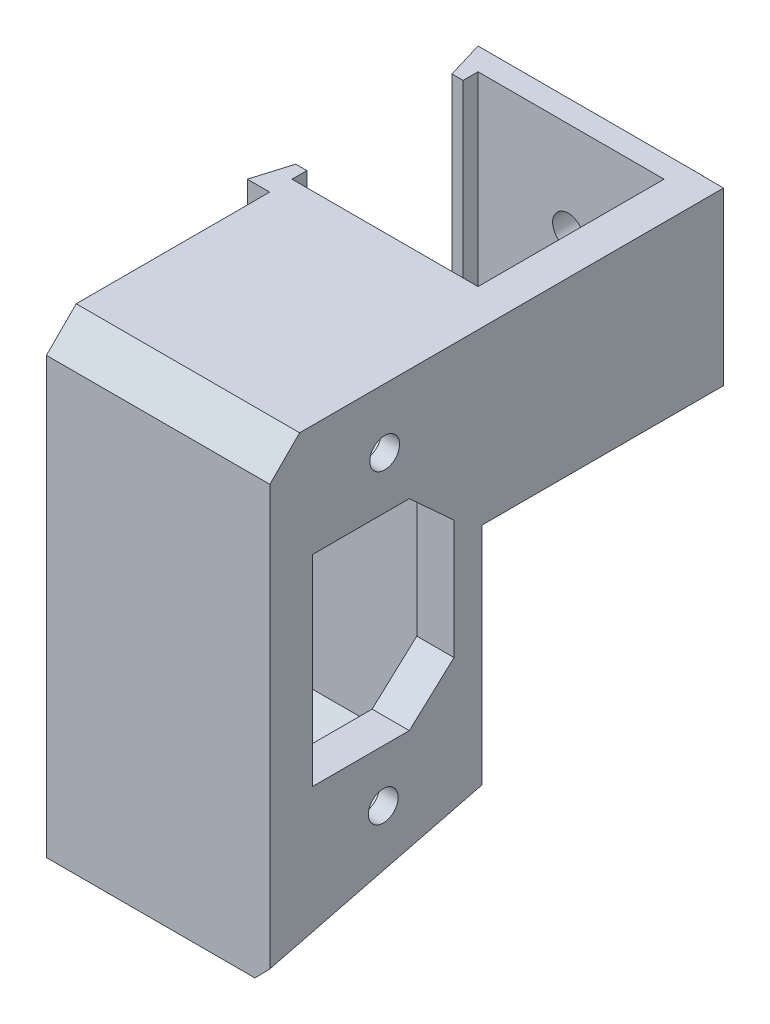
SolidWorks part; units mm, degrees
ref_plane "Спереди" through (0, 0, 0) normal (0, 0, 1) x (1, 0, 0)
ref_plane "Сверху" through (0, 0, 0) normal (0, 1, 0) x (1, 0, 0)
ref_plane "Справа" through (0, 0, 0) normal (1, 0, 0) x (0, 0, -1)
sketch "Эскиз1" plane through (0, 0, 0) normal (0, 1, 0) x (1, 0, 0)
  line L0 (-66.8258, 34.9697) -> (-66.8258, 29.9697)
  line L1 (-63.8258, 29.9697) -> (-63.8258, 31.9697)
  line L2 (-63.8258, 31.9697) -> (-38.8258, 31.9697)
  line L3 (-38.8258, 31.9697) -> (-38.8258, 6.9697)
  line L4 (-38.8258, 6.9697) -> (-63.8258, 6.9697)
  line L5 (-63.8258, 6.9697) -> (-63.8258, 8.9697)
  line L6 (-63.8258, 8.9697) -> (-66.8258, 8.9697)
  line L7 (-66.8258, 8.9697) -> (-66.8258, 3.9697)
  line L8 (-66.8258, 3.9697) -> (-22.1235, 3.9697)
  line L9 (-22.1235, 3.9697) -> (-36.579, 34.9697)
  line L10 (-36.579, 34.9697) -> (-66.8258, 34.9697)
  line L11 (-66.8258, 29.9697) -> (-63.8258, 29.9697)
  point P13 (0, 0)
  point P14 (-63.7308, 29.7758)
  dimension "D1" = 25
  dimension "D2" = 25
  dimension "D3" = 25
  dimension "D4" = 155
  dimension "D5" = 3
  dimension "D6" = 3
  dimension "D7" = 3
  dimension "D8" = 3
  dimension "D9" = 2
  dimension "D10" = 2
extrude "Бобышка-Вытянуть1" add sketch "Эскиз1" along normal blind 110
sketch "Эскиз3" plane through (0, 0, 0) normal (0, -1, 0) x (1, 0, 0)
  line L0 (-66.8258, -3.9697) -> (-65.3258, -8.9697)
  line L1 (-63.8258, -8.9697) -> (-66.8258, -8.9697) construction
  line L2 (-65.3258, -8.9697) -> (-66.8258, -8.9697)
  line L3 (-66.8258, -8.9697) -> (-66.8258, -3.9697)
  line L4 (-66.8258, -29.9697) -> (-66.8258, -34.9697)
  line L5 (-66.8258, -34.9697) -> (-65.3258, -29.9697)
  line L6 (-66.8258, -29.9697) -> (-63.8258, -29.9697) construction
  line L7 (-65.3258, -29.9697) -> (-66.8258, -29.9697)
extrude "Вырез-Вытянуть4" cut sketch "Эскиз3" against normal through all
sketch "Эскиз7" plane through (0, 0, 0) normal (0, -1, 0) x (-1, 0, 0)
  line L1 (36.0076, 1.3029) -> (19.3993, 1.3029)
  line L2 (36.0076, 1.3029) -> (36.0076, 39.7765)
  line L3 (36.0076, 39.7765) -> (19.3993, 39.7765)
  line L4 (19.3993, 1.3029) -> (19.3993, 39.7765)
extrude "Вырез-Вытянуть14" cut sketch "Эскиз7" against normal through all
sketch "Эскиз8" plane through (0, 0, 0) normal (0, -1, 0) x (-1, 0, 0)
  line L0 (66.8258, 3.9697) -> (36.0076, 3.9697) construction
  line L1 (38.7989, 3.9697) -> (33.7989, 3.9697)
  line L2 (38.7989, 3.9697) -> (38.7989, 34.9383)
  line L3 (38.7989, 34.9383) -> (33.7989, 34.9383)
  line L4 (33.7989, 3.9697) -> (33.7989, 34.9383)
  dimension "D1" = 5
extrude "Бобышка-Вытянуть2" add sketch "Эскиз8" against normal up to surface (110 mm away) up to face at (-54.2963, 110, -20.5678)
sketch "Эскиз10" plane through (0, 0, 0) normal (0, -1, 0) x (1, 0, 0)
  line L0 (-38.8258, -6.9697) -> (-63.8258, -6.9697) construction
  line L1 (-33.7989, -3.9697) -> (-38.7989, -3.9697)
  line L2 (-33.7989, -3.9697) -> (-33.7989, 22.0303)
  line L3 (-33.7989, 22.0303) -> (-38.7989, 22.0303)
  line L4 (-38.7989, -3.9697) -> (-38.7989, 22.0303)
  dimension "D1" = 5
  dimension "D2" = 29
extrude "Бобышка-Вытянуть4" add sketch "Эскиз10" against normal up to surface (110 mm away) up to face at (-52.7142, 110, -21.6795)
sketch "Эскиз16" plane through (0, 110, 0) normal (0, 1, 0) x (1, 0, 0)
  line L0 (-33.7989, 34.9383) -> (-33.7989, -22.0303) construction
  line L1 (-38.7989, -22.0303) -> (6.2011, -22.0303)
  line L2 (-38.7989, -22.0303) -> (-38.7989, -26.0303)
  line L3 (-38.7989, -26.0303) -> (6.2011, -26.0303)
  line L4 (6.2011, -22.0303) -> (6.2011, -26.0303)
  point P7 (6.2011, -24.0303)
  dimension "D1" = 40
  dimension "D2" = 4
extrude "Бобышка-Вытянуть7" add sketch "Эскиз16" against normal through all
sketch "Эскиз18" plane through (6.2011, 0, 0) normal (1, 0, 0) x (0, 0, -1)
  line L0 (34.9383, 110) -> (-22.0303, 110) construction
  line L1 (-53.1264, 60) -> (60.5458, 60)
  line L2 (-53.1264, 60) -> (-53.1264, -1.6498)
  line L3 (-53.1264, -1.6498) -> (60.5458, -1.6498)
  line L4 (60.5458, 60) -> (60.5458, -1.6498)
  dimension "D1" = 50
extrude "Вырез-Вытянуть18" cut sketch "Эскиз18" against normal through all
sketch "Эскиз19" plane through (0, 0, -34.9697) normal (0, 0, -1) x (-1, 0, 0)
  line L0 (66.8258, 85) -> (-6.2011, 85) construction
  line L1 (66.8258, 110) -> (66.8258, 60) construction
  line L2 (-6.2011, 60) -> (-6.2011, 110) construction
  line L3 (51.7024, 110) -> (51.7024, 60) construction
  line L4 (36.579, 110) -> (66.8258, 110) construction
  line L5 (36.579, 60) -> (66.8258, 60) construction
  line L6 (3.7989, 110) -> (3.7989, 60) construction
  line L7 (-6.2011, 110) -> (33.7989, 110) construction
  line L8 (33.7989, 60) -> (-6.2011, 60) construction
  circle A0 centre (51.7024, 85) radius 2.1
  circle A1 centre (3.7989, 85) radius 2
  dimension "D1" = 10
extrude "Вырез-Вытянуть19" cut sketch "Эскиз19" against normal through all
sketch "Эскиз22" plane through (0, 60, 0) normal (0, -1, 0) x (1, 0, 0)
  line L0 (-33.7989, -34.9383) -> (-33.7989, 22.0303) construction
  line L1 (-33.7989, -28.9697) -> (-8.7989, -28.9697)
  line L2 (-33.7989, -28.9697) -> (-33.7989, -31.9697)
  line L3 (-33.7989, -31.9697) -> (-8.7989, -31.9697)
  line L4 (-8.7989, -28.9697) -> (-8.7989, -31.9697)
  dimension "D1" = 3
  dimension "D2" = 3
  dimension "D3" = 25
extrude "Бобышка-Вытянуть10" add sketch "Эскиз22" against normal up to surface (50 mm away) up to face at (-44.6219, 110, -11.5218)
sketch "Эскиз23" plane through (0, 0, -31.9697) normal (0, 0, -1) x (-1, 0, 0)
  line L0 (8.7989, 85) -> (33.7989, 85) construction
  line L1 (8.7989, 110) -> (8.7989, 60) construction
  line L2 (33.7989, 110) -> (33.7989, 60) construction
  circle A0 centre (21.2989, 85) radius 2
extrude "Вырез-Вытянуть24" cut sketch "Эскиз23" against normal blind 10
sketch "Эскиз24" plane through (-62.4006, 0, -18.7202) normal (-0.9578, 0, -0.2873) x (-0.2873, 0, 0.9578)
  line L0 (-15.1624, 60) -> (30.8132, 60) construction
  line L1 (56.0839, 128.8367) -> (-38.7731, 128.8367)
  line L2 (56.0839, 128.8367) -> (56.0839, 97.5)
  line L3 (56.0839, 97.5) -> (-38.7731, 97.5)
  line L4 (-38.7731, 128.8367) -> (-38.7731, 97.5)
  line L5 (56.0839, 72.5) -> (-40.8308, 72.5)
  line L6 (56.0839, 72.5) -> (56.0839, 38.7983)
  line L7 (56.0839, 38.7983) -> (-40.8308, 38.7983)
  line L8 (-40.8308, 72.5) -> (-40.8308, 38.7983)
  line L9 (-15.1624, 110) -> (30.8132, 110) construction
  dimension "D1" = 12.5
  dimension "D2" = 12.5
extrude "Вырез-Вытянуть25" cut sketch "Эскиз24" against normal through all and the other way through all
sketch "Эскиз26" plane through (0, 60, 0) normal (0, -1, 0) x (1, 0, 0)
  line L5 (-33.7989, -34.9383) -> (8.2572, -34.9383)
  line L6 (-33.7989, -34.9383) -> (-33.7989, 31.6395)
  line L7 (-33.7989, 31.6395) -> (8.2572, 31.6395)
  line L8 (8.2572, -34.9383) -> (8.2572, 31.6395)
extrude "Вырез-Вытянуть26" cut sketch "Эскиз26" against normal through all
sketch "Эскиз27" plane through (-33.7989, 0, 0) normal (1, 0, 0) x (0, 0, -1)
  line L0 (-26.0303, 72.5) -> (4.4497, 72.5)
  line L1 (34.9383, 72.5) -> (-26.0303, 72.5) construction
  line L2 (4.4497, 72.5) -> (4.4497, 42.7)
  line L3 (4.4497, 42.7) -> (-26.0303, 35.044)
  line L4 (-26.0303, 35.044) -> (-26.0303, 72.5)
  line L5 (4.4497, 42.7) -> (4.4497, 22.2789) construction
  dimension "D1" = 30.48
  dimension "D2" = 29.8
  dimension "D3" = 75.9
extrude "Бобышка-Вытянуть11" add sketch "Эскиз27" against normal blind 5
sketch "Эскиз28" plane through (-33.7989, 0, 0) normal (1, 0, 0) x (0, 0, -1)
  line L0 (-10.7903, 38.872) -> (-10.7903, 99.058) construction
  line L1 (-26.0303, 35.044) -> (4.4497, 42.7) construction
  line L2 (-10.7903, 68.965) -> (-26.0303, 68.965) construction
  line L3 (-26.0303, 97.5) -> (-26.0303, 35.044) construction
  line L4 (-26.0303, 68.965) -> (4.4497, 68.965) construction
  line L5 (4.4497, 42.7) -> (4.4497, 72.5) construction
  line L6 (-17.241, 89.465) -> (-3.9662, 89.465) construction
  line L7 (-17.241, 48.465) -> (-3.9662, 48.465) construction
  line L9 (-20.2903, 82.465) -> (-1.2903, 82.465)
  line L10 (-20.2903, 82.465) -> (-20.2903, 55.465)
  line L11 (-20.2903, 55.465) -> (-1.2903, 55.465)
  line L12 (-1.2903, 82.465) -> (-1.2903, 55.465)
  circle A0 centre (-10.6036, 89.465) radius 2
  circle A1 centre (-10.7903, 48.465) radius 2
  dimension "D3" = 13.5
  dimension "D1" = 20.5
  dimension "D2" = 20.5
  dimension "D4" = 13.5
  dimension "D5" = 9.5
  dimension "D6" = 9.5
extrude "Вырез-Вытянуть27" cut sketch "Эскиз28" against normal through all
sketch "Эскиз29" plane through (-33.7989, 0, 0) normal (1, 0, 0) x (0, 0, -1)
  line L0 (-10.7903, 82.465) -> (-10.7903, 55.465) construction
  line L1 (-1.2903, 82.465) -> (-20.2903, 82.465) construction
  line L2 (-20.2903, 55.465) -> (-1.2903, 55.465) construction
  line L3 (-20.2903, 68.965) -> (-1.2903, 68.965) construction
  line L4 (-20.2903, 82.465) -> (-20.2903, 55.465) construction
  line L5 (-1.2903, 55.465) -> (-1.2903, 82.465) construction
  line L6 (-7.2903, 82.465) -> (-1.2903, 82.465)
  line L7 (-1.2903, 82.465) -> (-1.2903, 76.965)
  line L8 (-1.2903, 76.965) -> (-7.2903, 82.465)
  line L9 (-1.2903, 60.965) -> (-7.2903, 55.465)
  line L10 (-7.2903, 55.465) -> (-1.2903, 55.465)
  line L11 (-1.2903, 55.465) -> (-1.2903, 60.965)
  point P18 (0, 0)
  point P20 (0, 0)
  dimension "D1" = 8
  dimension "D2" = 8
  dimension "D3" = 13
  dimension "D4" = 13
extrude "Бобышка-Вытянуть13" add sketch "Эскиз29" against normal blind 5
sketch "Эскиз30" plane through (-38.7989, 0, 0) normal (-1, 0, 0) x (0, 0, 1)
  line L0 (-4.4497, 42.7) -> (-4.4497, 97.5)
  line L1 (-4.4497, 42.7) -> (-4.4497, 72.5) construction
  line L2 (-3.9697, 97.5) -> (-8.9697, 97.5) construction
  line L3 (-4.4497, 97.5) -> (-1.4497, 97.5)
  line L4 (-3.9697, 97.5) -> (26.0303, 97.5) construction
  line L5 (-1.4497, 97.5) -> (-1.4497, 45.0396)
  line L6 (-1.4497, 45.0396) -> (26.0303, 38.1371)
  line L7 (26.0303, 35.044) -> (26.0303, 97.5) construction
  line L8 (26.0303, 38.1371) -> (26.0303, 35.044)
  line L9 (26.0303, 35.044) -> (-4.4497, 42.7) construction
  line L10 (26.0303, 35.044) -> (-4.4497, 42.7)
  dimension "D1" = 3
  dimension "D2" = 104.1
  dimension "D3" = 3
extrude "Бобышка-Вытянуть14" add sketch "Эскиз30" along normal up to surface (25.0268 mm away) up to face at (-63.8258, 85, -7.9697)
ref_plane "Плоскость4" through (-38.7989, 38.1371, 26.0303) normal (0, 0.2436, -0.9699) x (-1, 0, 0)
sketch "Эскиз32" plane through (-38.7989, 0, 0) normal (-1, 0, 0) x (0, 0, 1)
  line L0 (-1.4497, 97.5) -> (26.0303, 97.5)
  line L1 (-1.4497, 97.5) -> (-1.4497, 95.5)
  line L2 (-1.4497, 45.0396) -> (-1.4497, 97.5) construction
  line L3 (-1.4497, 95.5) -> (24.0303, 95.5)
  line L4 (24.0303, 95.5) -> (24.0303, 38.6395)
  line L5 (26.0303, 38.1371) -> (-1.4497, 45.0396) construction
  line L6 (24.0303, 38.6395) -> (26.0303, 38.1371)
  line L7 (27.9284, 45.6941) -> (24.1321, 30.5801) construction
  line L8 (26.0303, 38.1371) -> (26.0303, 97.5)
  dimension "D1" = 2
  dimension "D2" = 2
extrude "Бобышка-Вытянуть15" add sketch "Эскиз32" along normal up to surface (25.0268 mm away) up to face at (-63.8258, 62.6151, 4.0403)
chamfer "Фаска1" distance 4 angle 45 1 edges at (-48.8124, 97.5, 26.0303)
chamfer "Фаска2" distance 3 angle 45 1 edges at (-51.3124, 95.5, 24.0303)
sketch "Эскиз33" plane through (-38.7989, 0, 0) normal (-1, 0, 0) x (0, 0, 1)
  line L1 (10.6036, 93.5064) -> (7.1036, 91.4857)
  line L2 (7.1036, 91.4857) -> (7.1036, 87.4442)
  line L3 (7.1036, 87.4442) -> (10.6036, 85.4235)
  line L4 (10.6036, 85.4235) -> (14.1036, 87.4442)
  line L5 (14.1036, 87.4442) -> (14.1036, 91.4857)
  line L6 (14.1036, 91.4857) -> (10.6036, 93.5064)
  line L7 (10.7903, 52.5064) -> (7.2903, 50.4857)
  line L8 (7.2903, 50.4857) -> (7.2903, 46.4442)
  line L9 (7.2903, 46.4442) -> (10.7903, 44.4235)
  line L10 (10.7903, 44.4235) -> (14.2903, 46.4442)
  line L11 (14.2903, 46.4442) -> (14.2903, 50.4857)
  line L12 (14.2903, 50.4857) -> (10.7903, 52.5064)
  circle A0 centre (10.6036, 89.465) radius 3.5 construction
  circle A1 centre (10.7903, 48.465) radius 3.5 construction
extrude "Вырез-Вытянуть28" cut sketch "Эскиз33" against normal blind 2.5
chamfer "Фаска3" distance 2 angle 45 2 edges at (-33.7989, 57.6, -4.4497) (-33.7989, 72.5, -19.694)
chamfer "Фаска4" distance 2 angle 45 1 edges at (-33.7989, 38.6208, 11.7903)
